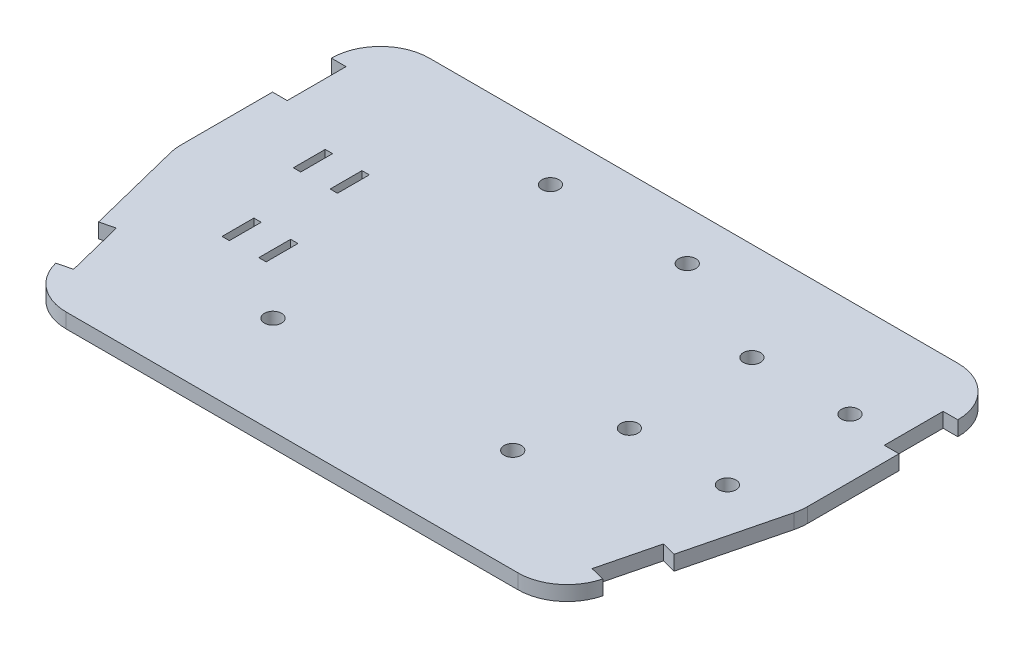
SolidWorks part; units mm, degrees
ref_plane "Front Plane" through (0, 0, 0) normal (0, 0, 1) x (1, 0, 0)
ref_plane "Top Plane" through (0, 0, 0) normal (0, 1, 0) x (1, 0, 0)
ref_plane "Right Plane" through (0, 0, 0) normal (1, 0, 0) x (0, 0, -1)
sketch "Sketch1" plane through (0, 0, 0) normal (0, 1, 0) x (1, 0, 0)
  line L0 (-19.2, 30.95) -> (8.7, 30.95) construction
  line L1 (-63.9, -40.95) -> (63.9, -40.95)
  line L2 (-63.9, -40.95) -> (-63.9, 40.95)
  line L3 (-63.9, 40.95) -> (63.9, 40.95)
  line L4 (63.9, -40.95) -> (63.9, 40.95)
  line L5 (-63.9, -40.95) -> (63.9, 40.95) construction
  line L6 (-63.9, 40.95) -> (63.9, -40.95) construction
  line L7 (-63.9, -0.95) -> (-53.9, -40.95)
  line L8 (53.9, -40.95) -> (63.9, -0.95)
  circle A0 centre (-19.2, 30.95) radius 3
  circle A1 centre (8.7, 30.95) radius 3
  circle A2 centre (-23.9, -20.95) radius 3
  circle A3 centre (23.9, -19.85) radius 3
  point P0 (0, 0)
  dimension "D1" = 6
  dimension "D2" = 50.8
  dimension "D3" = 27.9
  dimension "D4" = 51.9
  dimension "D5" = 15.2
  dimension "D6" = 4.7
  dimension "D7" = 20
  dimension "D8" = 40
  dimension "D9" = 40
  dimension "D10" = 10
  dimension "D11" = 10
  dimension "D12" = 10
  dimension "D13" = 40
  dimension "D14" = 40
extrude "Boss-Extrude1" add sketch "Sketch1" along normal blind 3 contours L1 L8 L4 L3 L2 L7 A3 A2 A1 A0 | A2 | A3 | A0 | A1 region at (0.0298, 0, -1.0499) region at (-19.2, 0, -30.95) region at (8.7, 0, -30.95) region at (-23.9, 0, 20.95) region at (23.9, 0, 19.85)
extrude "Boss-Extrude2" add sketch "Sketch1<3>" against normal blind 3 contours A2 | A3 | A0 | A1 region at (-19.2, 0, -30.95) region at (8.7, 0, -30.95) region at (-23.9, 0, 20.95) region at (23.9, 0, 19.85)
sketch "Sketch1<3>" plane through (0, 0, 0) normal (0, 1, 0) x (1, 0, 0) same geometry as "Sketch1"
sketch "Sketch3" plane through (0, -3, 0) normal (0, -1, 0) x (1, 0, 0)
  circle A0 centre (-19.2, -30.95) radius 3 construction
  circle A1 centre (-23.9, 20.95) radius 3 construction
  circle A2 centre (23.9, 19.85) radius 3 construction
  circle A3 centre (8.7, -30.95) radius 3 construction
  circle A4 centre (-19.2, -30.95) radius 3
  circle A5 centre (-23.9, 20.95) radius 3
  circle A6 centre (23.9, 19.85) radius 3
  circle A7 centre (8.7, -30.95) radius 3
  circle A8 centre (-23.9, 20.95) radius 1.75
  circle A9 centre (23.9, 19.85) radius 1.75
  circle A10 centre (8.7, -30.95) radius 1.75
  circle A11 centre (-19.2, -30.95) radius 1.75
  point P16 (0, 0)
  dimension "D1" = 3.5
extrude "Cut-Extrude1" cut sketch "Sketch3" against normal through all contours A10 | A11 | A9 | A8 region at (-23.9, -3, 20.95) region at (23.9, -3, 19.85) region at (8.7, -3, -30.95) region at (-19.2, -3, -30.95)
fillet "Fillet1" radius 10 6 edges at (-63.9, 1.5, -40.95) (63.9, 1.5, -40.95) (63.9, 1.5, 0.95) (53.9, 1.5, 40.95) (-63.9, 1.5, 0.95) (-53.9, 1.5, 40.95)
sketch "Sketch4" plane through (0, 3, 0) normal (0, 1, 0) x (1, 0, 0)
  line L0 (31.9, 20.95) -> (51.9, 20.95) construction
  line L1 (51.9, 20.95) -> (51.9, -4.05) construction
  line L2 (51.9, -4.05) -> (31.9, -4.05) construction
  line L3 (-53.9, 40.95) -> (53.9, 40.95) construction
  line L4 (63.9, 0.2811) -> (63.9, 30.95) construction
  circle A0 centre (51.9, 20.95) radius 1.75
  circle A1 centre (31.9, 20.95) radius 1.75
  circle A2 centre (51.9, -4.05) radius 1.75
  circle A3 centre (31.9, -4.05) radius 1.75
  dimension "D1" = 3.5
  dimension "D2" = 20
  dimension "D3" = 20
  dimension "D4" = 25
  dimension "D5" = 12
extrude "Cut-Extrude2" cut sketch "Sketch4" against normal through all
sketch "Sketch5" plane through (0, 3, 0) normal (0, 1, 0) x (1, 0, 0)
  line L0 (-47.65, 10.95) -> (-40.15, 10.95) construction
  line L1 (-46.9, 14.2) -> (-48.4, 14.2)
  line L2 (-46.9, 14.2) -> (-46.9, 7.7)
  line L3 (-46.9, 7.7) -> (-48.4, 7.7)
  line L4 (-48.4, 14.2) -> (-48.4, 7.7)
  line L5 (-46.9, 14.2) -> (-48.4, 7.7) construction
  line L6 (-46.9, 7.7) -> (-48.4, 14.2) construction
  line L7 (-40.9, 7.7) -> (-39.4, 7.7)
  line L8 (-40.9, 7.7) -> (-40.9, 14.2)
  line L9 (-40.9, 14.2) -> (-39.4, 14.2)
  line L10 (-39.4, 7.7) -> (-39.4, 14.2)
  line L11 (-40.9, 7.7) -> (-39.4, 14.2) construction
  line L12 (-40.9, 14.2) -> (-39.4, 7.7) construction
  line L13 (-53.9, 40.95) -> (53.9, 40.95) construction
  line L15 (-63.9, 0.2811) -> (-63.9, 30.95) construction
  point P0 (-47.65, 10.95)
  point P5 (-40.15, 10.95)
  point P12 (-43.9, 10.95)
  point P17 (-63.9, 28.4033)
  dimension "D1" = 1.5
  dimension "D2" = 6.5
  dimension "D3" = 7.5
  dimension "D4" = 30
  dimension "D5" = 20
extrude "Cut-Extrude3" cut sketch "Sketch5" against normal through all
pattern_linear "LPattern1" count 2 spacing 20 along (0.2425, 0, 0.9701) of "Cut-Extrude3"
sketch "Sketch6" plane through (0, 3, 0) normal (0, 1, 0) x (1, 0, 0)
  line L0 (58.7041, -21.7336) -> (55.7937, -21.006)
  line L1 (-63.9, 30.95) -> (-60.9, 30.95)
  line L2 (-63.9, 30.95) -> (-63.9, 18.95)
  line L3 (-63.9, 18.95) -> (-60.9, 18.95)
  line L4 (-60.9, 30.95) -> (-60.9, 18.95)
  line L5 (-58.7041, -21.7336) -> (-55.7937, -21.006)
  line L6 (63.9, 30.95) -> (60.9, 30.95)
  line L7 (63.9, 30.95) -> (63.9, 18.95)
  line L8 (63.9, 18.95) -> (60.9, 18.95)
  line L9 (60.9, 30.95) -> (60.9, 18.95)
  line L10 (-63.6014, -2.1443) -> (-55.7937, -33.3754) construction
  line L11 (-55.7937, -21.006) -> (-52.8832, -32.6477)
  line L12 (-52.8832, -32.6477) -> (-55.7937, -33.3754)
  line L13 (-55.7937, -33.3754) -> (-58.7041, -21.7336)
  line L14 (55.7937, -33.3754) -> (63.6014, -2.1443) construction
  line L15 (55.7937, -21.006) -> (52.8832, -32.6477)
  line L16 (52.8832, -32.6477) -> (55.7937, -33.3754)
  line L17 (55.7937, -33.3754) -> (58.7041, -21.7336)
  dimension "D1" = 3
  dimension "D2" = 12
  dimension "D3" = 3
  dimension "D4" = 12
extrude "Cut-Extrude4" cut sketch "Sketch6" against normal through all
